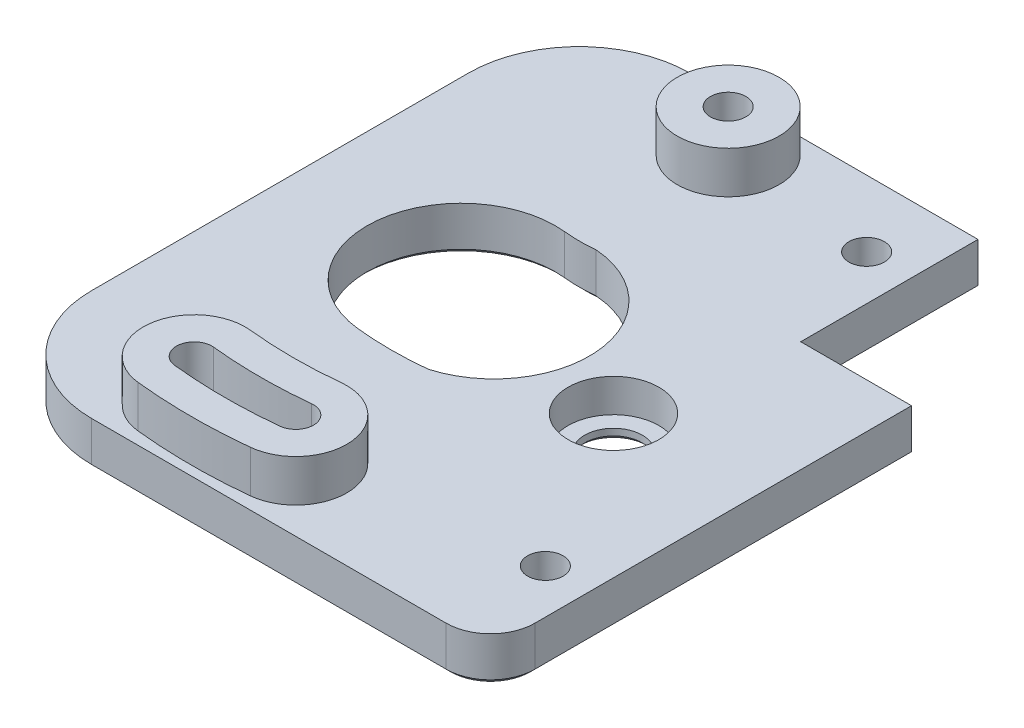
SolidWorks part; units mm, degrees
ref_plane "前视基准面" through (0, 0, 0) normal (0, 0, 1) x (1, 0, 0)
ref_plane "上视基准面" through (0, 0, 0) normal (0, 1, 0) x (1, 0, 0)
ref_plane "右视基准面" through (0, 0, 0) normal (1, 0, 0) x (0, 0, -1)
other "Configuration Table"
sketch "草图1" plane through (0, 0, 0) normal (0, 1, 0) x (1, 0, 0)
  line L1 (0, 0) -> (46, 0)
  line L2 (0, 0) -> (0, 54)
  line L3 (0, 54) -> (46, 54)
  line L4 (46, 0) -> (46, 54)
  dimension "D1" = 46
  dimension "D2" = 54
extrude "凸台-拉伸1" add sketch "草图1" along normal blind 4
sketch "草图2" plane through (0, 0, 0) normal (0, -1, 0) x (-1, 0, 0)
  line L0 (0, 54) -> (0, 0) construction
  line L1 (-46, 54) -> (0, 54) construction
  circle A0 centre (-18.15, 49.3) radius 1.6
  circle A1 centre (-18.15, 5.45) radius 1.6
  circle A2 centre (-18.15, 27.375) radius 8.5
  circle A3 centre (-33.15, 23.95) radius 4.1
  point P6 (0, 27)
  point P9 (-23, 54)
  dimension "D7" = 17
  dimension "D10" = 8.2
  dimension "D11" = 3.2
  dimension "D12" = 3.2
  dimension "D1" = 22.3
  dimension "D2" = 4.85
  dimension "D3" = 0
  dimension "D4" = 43.85
  dimension "D5" = 0
  dimension "D6" = 21.925
  dimension "D8" = 15
  dimension "D9" = 18.5
extrude "切除-拉伸1" cut sketch "草图2" against normal through all
sketch "草图4" plane through (0, 0, 0) normal (0, -1, 0) x (-1, 0, 0)
  circle A0 centre (-33.15, 23.95) radius 4.1
  circle A1 centre (-33.15, 23.95) radius 2.6
  dimension "D1" = 5.2
extrude "凸台-拉伸2" add sketch "草图4" against normal blind 1
sketch "草图5" plane through (0, 4, 0) normal (0, 1, 0) x (1, 0, 0)
  line L0 (46, 0) -> (46, 54) construction
  line L1 (46, 54) -> (36, 54)
  line L2 (46, 54) -> (46, 38)
  line L3 (46, 38) -> (36, 38)
  line L4 (36, 54) -> (36, 38)
  line L5 (46, 54) -> (0, 54) construction
  dimension "D1" = 16
  dimension "D2" = 10
extrude "切除-拉伸2" cut sketch "草图5" against normal through all
sketch "草图6" plane through (0, 0, 0) normal (0, -1, 0) x (-1, 0, 0)
  circle A0 centre (-18.15, 49.3) radius 43.85 construction
  circle A7 centre (-18.15, 49.3) radius 21.925 construction
  arc A8 (-22.5663, 7.2814) -> (-13.7337, 7.2814) centre (-18.15, 49.3) ccw
  arc A10 (-21.3303, 19.0417) -> (-14.9697, 19.0417) centre (-18.15, 49.3) ccw
  arc A11 (-19.5533, 35.9485) -> (-16.7467, 35.9485) centre (-18.15, 49.3) ccw
  arc A13 (-19.5533, 35.9485) -> (-21.3303, 19.0417) centre (-18.9549, 27.3388) ccw
  arc A14 (-14.9697, 19.0417) -> (-16.7467, 35.9485) centre (-15.8582, 27.4951) ccw
  arc A17 (-22.9008, 4.099) -> (-13.3992, 4.099) centre (-18.15, 49.3) ccw
  arc A18 (-22.5663, 7.2814) -> (-22.9008, 4.099) centre (-22.7336, 5.6902) ccw
  arc A19 (-13.3992, 4.099) -> (-13.7337, 7.2814) centre (-13.5664, 5.6902) ccw
  point P4 (-18.15, 49.3)
  point P5 (24.1, 49.3)
  point P6 (-18.15, 49.3)
  point P8 (27.3, 49.3)
  point P15 (-18.15, 49.3)
  point P18 (-18.15, 49.3)
  point P21 (-18.15, 49.3)
  point P24 (-18.15, 49.3)
  point P31 (-18.15, 49.3)
  point P34 (-18.15, 49.3)
extrude "切除-拉伸3" cut sketch "草图6" against normal blind 10
sketch "草图7" plane through (0, 4, 0) normal (0, 1, 0) x (1, 0, 0)
  circle A1 centre (18.15, 49.3) radius 4.6
  circle A2 centre (18.15, 49.3) radius 1.6
  circle A3 centre (18.15, 49.3) radius 1.6
  arc A13 (14.0473, 10.265) -> (22.2527, 10.265) centre (18.15, 49.3) ccw
  arc A14 (23.2144, 1.1154) -> (22.2527, 10.265) centre (22.7336, 5.6902) ccw
  arc A15 (13.0856, 1.1154) -> (23.2144, 1.1154) centre (18.15, 49.3) ccw
  arc A16 (14.0473, 10.265) -> (13.0856, 1.1154) centre (13.5664, 5.6902) ccw
  arc A17 (22.9008, 4.099) -> (22.5663, 7.2814) centre (22.7336, 5.6902) ccw
  arc A18 (13.7337, 7.2814) -> (13.3992, 4.099) centre (13.5664, 5.6902) ccw
  arc A19 (13.3992, 4.099) -> (22.9008, 4.099) centre (18.15, 49.3) ccw
  arc A20 (13.7337, 7.2814) -> (22.5663, 7.2814) centre (18.15, 49.3) ccw
  arc A21 (22.9008, 4.099) -> (22.5663, 7.2814) centre (22.7336, 5.6902) ccw
  arc A22 (13.7337, 7.2814) -> (13.3992, 4.099) centre (13.5664, 5.6902) ccw
  arc A23 (13.3992, 4.099) -> (22.9008, 4.099) centre (18.15, 49.3) ccw
  arc A24 (13.7337, 7.2814) -> (22.5663, 7.2814) centre (18.15, 49.3) ccw
  dimension "D1" = 0
  dimension "D2" = 3
  dimension "D3" = 0
  dimension "D4" = 3
extrude "凸台-拉伸3" add sketch "草图7" along normal blind 3.8
sketch "草图10" plane through (0, 4, 0) normal (0, 1, 0) x (1, 0, 0)
  line L0 (46, 0) -> (46, 38) construction
  line L1 (0, 0) -> (46, 0) construction
  circle A1 centre (42, 8.95) radius 1.6
  dimension "D1" = 4
  dimension "D2" = 8.95
  dimension "D3" = 3.2
extrude "切除-拉伸6" cut sketch "草图10" against normal through all
sketch "草图11" plane through (0, 4, 0) normal (0, 1, 0) x (1, 0, 0)
  line L1 (36, 54) -> (0, 54) construction
  circle A0 centre (31.95, 48) radius 1.6
  circle A1 centre (18.15, 49.3) radius 4.6 construction
  dimension "D1" = 3.2
  dimension "D2" = 13.8
  dimension "D3" = 6
extrude "切除-拉伸7" cut sketch "草图11" against normal through all
fillet "圆角1" radius 10 2 edges at (0, 2, -54) (0, 2, 0)
fillet "圆角2" radius 4 1 edges at (46, 2, 0)
chamfer "倒角1" distance 0.4 angle 45 21 edges at (7.4048, 0, -28.3836) (18.15, 0, -35.875) (27.5381, 0, -28.241) (18.15, 0, -18.875) (33.15, 0, -26.55) (18.15, 0, -50.9) (41, 0, -38) (36, 0, -46) (23, 0, -54) (2.9289, 0, -51.0711) (0, 0, -27) (2.9289, 0, -2.9289) (26, 0, 0) (44.8284, 0, -1.1716) (46, 0, -21) (42, 0, -7.35) (31.95, 0, -46.4) (11.9752, 0, -5.8575) (18.15, 0, -7.05) (24.3248, 0, -5.8575) (18.15, 0, -3.85)
equation "\"D6@草图2\"=\"D4@草图2\"/2"
equation "\"D1@凸台-拉伸2\"=3.60-2.6"
